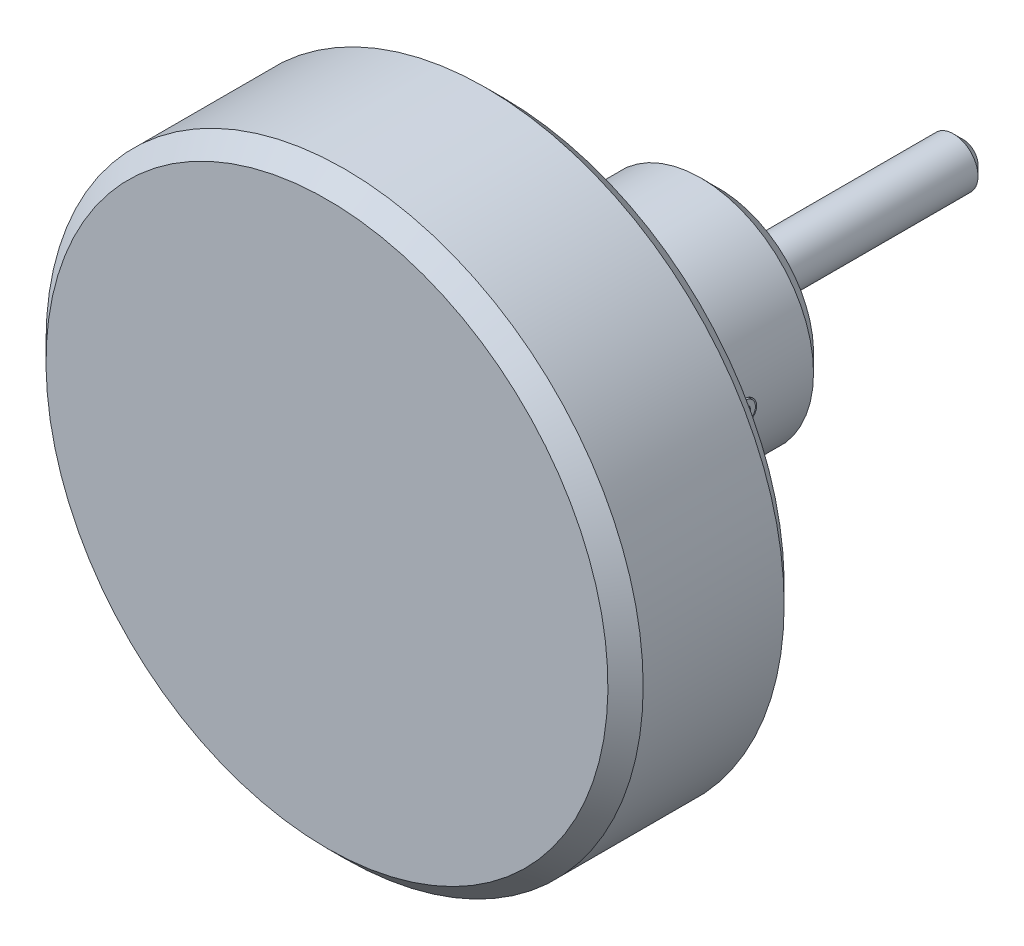
SolidWorks part; units mm, degrees
ref_plane "Front" through (0, 0, 0) normal (0, 0, 1) x (1, 0, 0)
ref_plane "Top" through (0, 0, 0) normal (0, 1, 0) x (1, 0, 0)
ref_plane "Right" through (0, 0, 0) normal (1, 0, 0) x (0, 0, -1)
sketch "Sketch0" plane through (0, 0, 0) normal (1, 0, 0) x (0, 0, -1)
  line L0 (12.5, 0) -> (-12.5, 0) construction
  line L1 (-22.4906, 0) -> (-21.9826, 0) construction
  line L2 (12.4375, 2.6083) -> (12.9375, 1.7422) construction
  line L3 (12.9375, 1.7422) -> (13.4375, 2.6083) construction
  line L4 (-12.5, 2.5) -> (12.5, 2.5) construction
  line L5 (12.5, 2.5) -> (12.5, 0) construction
  line L6 (-12.5, 0) -> (-12.5, 2.5) construction
  line L8 (13.4375, 2.6083) -> (12.4375, 2.6083) construction
  line L9 (12.9375, 1.7422) -> (12.9375, 1.8505) construction
  line L10 (-12.5, -2.5) -> (12.5, -2.5) construction
  line L11 (12.9375, 2.6083) -> (12.9375, 2.5) construction
  line L12 (12.5, 2.5) -> (13.375, 2.5) construction
  line L13 (12.4688, 2.5541) -> (13.4062, 2.5541) construction
  line L14 (12.875, 1.8505) -> (13, 1.8505) construction
  line L15 (-12.5, 0) -> (-52.5, 0) construction
  line L16 (-52.5, -30.5) -> (-52.5, 30.5) construction
  line L17 (-52.5, 30.5) -> (-34.5, 30.5) construction
  line L18 (-34.5, 30.5) -> (-34.5, 11.5) construction
  line L19 (-34.5, 11.5) -> (-12.5, 11.5) construction
  line L20 (-12.5, 11.5) -> (-12.5, 0) construction
  circle A0 centre (-21.3, 0) radius 1.1906
  point P2 (-21.3, 0)
  point P17 (8, -2.5)
  point P18 (12.9375, 2.5)
  point P19 (0, 0)
  point P22 (12.9375, 2.5541)
  point P26 (12.9375, 1.8505)
  point P43 (-52.5, 0)
  dimension "Roll Pin Diameter" = 2.3813
  dimension "Thread Pitch" = 1
  dimension "D1" = 0.125
  dimension "D2" = 4.5
  dimension "Stud Diameter | Thread Size" = 5
  dimension "Head Height" = 18
  dimension "Head Diameter" = 61
  dimension "Hub Diameter" = 23
  dimension "Stud Length" = 25
  dimension "D3" = 8.8
  dimension "Roll Pin Wall Thickness" = 0.508
  dimension "Hub Height" = 22
sketch "Sketch1" plane through (0, 0, 0) normal (1, 0, 0) x (0, 0, -1)
  line L0 (12.5, 0) -> (-12.5, 0)
  line L4 (-12.5, 2.5) -> (12.5, 2.5)
  line L5 (12.5, 2.5) -> (12.5, 0)
  line L6 (-12.5, 0) -> (-12.5, 2.5)
revolve "Revolve1" add sketch "Sketch1" angle 360 about L0
sketch "Sketch5" plane through (0, 0, 0) normal (1, 0, 0) x (0, 0, -1)
  line L2 (-12.5, 11.5) -> (-34.5, 11.5)
  line L3 (-34.5, 11.5) -> (-34.5, 30.5)
  line L7 (-52.5, 0) -> (-12.5, 0) construction
  line L10 (-12.5, 11.5) -> (-12.5, 0)
  line L12 (-52.5, 30.5) -> (-34.5, 30.5)
  line L13 (-52.5, 30.5) -> (-52.5, 0)
  line L18 (-12.5, 0) -> (-52.5, 0)
revolve "Revolve3" add sketch "Sketch5" angle 360 about L18
chamfer "Chamfer1" distance 1 angle 45 1 edges at (-2.5, 0, -12.5)
chamfer "Chamfer2" distance 1.8 angle 45 3 edges at (0, 30.5, 34.5) (0, 30.5, 52.5) (0, 11.5, 12.5)
ref_plane "Plane3" through (0, 0, 21.3) normal (0, 0, 1) x (1, 0, 0)
sketch "Sketch16" plane through (0, 0, 21.3) normal (0, 0, 1) x (1, 0, 0)
  line L0 (11.5, 0) -> (1.975, 0)
  line L1 (11.5, 0) -> (11.5, 1.1906)
  line L2 (11.5, 1.1906) -> (1.975, 1.1906)
  line L3 (1.975, 1.1906) -> (1.975, 0)
  circle A0 centre (0, 0) radius 11.5 construction
  circle A1 centre (0, 0) radius 11.5 construction
  point P9 (0, 1.1906)
  dimension "Roll Pin Length" = 9.525
revolve "Cut-Revolve1" cut sketch "Sketch16" angle 360 about L0
sketch "Sketch17" plane through (0, 0, 21.3) normal (0, 0, 1) x (1, 0, 0)
  line L0 (11.5, 1.0656) -> (10.0712, 1.1906)
  line L1 (11.5, 0) -> (11.5, 1.1906) construction
  line L2 (11.5, 1.1906) -> (1.975, 1.1906) construction
  line L3 (10.0712, 1.1906) -> (3.4037, 1.1906)
  line L4 (3.4037, 1.1906) -> (1.975, 1.0656)
  line L5 (1.975, 1.1906) -> (1.975, 0) construction
  line L6 (1.975, 1.0656) -> (1.975, 0.5576)
  line L7 (1.975, 0.5576) -> (3.4037, 0.6826)
  line L8 (3.4037, 0.6826) -> (10.0713, 0.6826)
  line L9 (10.0713, 0.6826) -> (11.5, 0.5576)
  line L10 (11.5, 0.5576) -> (11.5, 1.0656)
  dimension "D1" = 0.508
  dimension "D2" = 5
  dimension "D3" = 1.4287
  dimension "D4" = 0.508
revolve "Revolve4" add sketch "Sketch17" angle 325 mid plane about L0
split "Split1" [suppressed] bodies to split 158
sketch "Sketch13" [suppressed] plane through (0, 0, -10) normal (0, 0, -1) x (-1, 0, 0)
  circle A0 centre (0, 0) radius 2.5 construction
  circle A1 centre (0, 0) radius 2.5
curve "Helix/Spiral1" [suppressed]
sketch "Sketch14" [suppressed] plane through (0, 0, 0) normal (1, 0, 0) x (0, 0, -1)
  line L0 (9.9688, 2.5541) -> (10.9062, 2.5541)
  line L1 (10.9062, 2.5541) -> (10.5, 1.8505)
  line L2 (10.5, 1.8505) -> (10.375, 1.8505)
  line L3 (10.375, 1.8505) -> (9.9688, 2.5541)
sweep "Cut-Sweep1" [suppressed] cut profiles "Sketch14" path "Helix/Spiral1"
sketch "Sketch15" [suppressed] plane through (0, 0, 10) normal (0, 0, -1) x (-1, 0, 0)
  circle A1 centre (0, 0) radius 2.5
  circle A2 centre (0, 0) radius 2.5
  dimension "D1" = 0
extrude "Boss-Extrude1" [suppressed] add sketch "Sketch15" along normal blind 10 draft 45
sketch "Sketch18" [suppressed] plane through (0, 0, 26) normal (0, 0, 1) x (1, 0, 0)
  line L0 (0, 9.5) -> (0, 9.3) construction
  line L1 (0, 9.3) -> (-0.1658, 9.5)
  line L2 (-0.1658, 9.5) -> (0.1658, 9.5)
  line L3 (0.1658, 9.5) -> (0, 9.3)
  line L4 (-0.1658, 9.5) -> (0, 0) construction
  line L5 (0, 0) -> (0.1658, 9.5) construction
  line L6 (0, 9.1) -> (0, 8.9) construction
  line L7 (0, -9.5) -> (0, 9.5) construction
  line L8 (0, 9.1) -> (0, 9.3) construction
  circle A2 centre (0, 0) radius 8.9 construction
  circle A3 centre (0, 0) radius 9.5 construction
  dimension "D1" = 2
sketch "Sketch19" [suppressed] plane through (0, 0, 26) normal (0, 0, 1) x (1, 0, 0)
  circle A0 centre (0, 0) radius 9.5 construction
  circle A1 centre (0, 0) radius 9.5
curve "Helix/Spiral2" [suppressed] pitch 216 height 18 turns 0.0833
sweep "Cut-Sweep2" [suppressed] cut profiles "Sketch18" path "Helix/Spiral2"
pattern_circular "CirPattern1" [suppressed] count 54 over 360 about axis through (0, 0, 12.5) along (0, 0, 1) reverse direction yes of bodies 160
mirror "Mirror1" [suppressed] about plane through (0, 0, 0) normal (1, 0, 0)
equation "\"D1@Chamfer1\" = \"Thread Pitch@Sketch0\""
equation "\"D4@Helix/Spiral1\" = \"Thread Pitch@Sketch0\""
equation "\"D3@Helix/Spiral1\" = \"Thread Pitch@Sketch0\" + \"Stud Length@Sketch0\""
equation "\"D1@Sketch0\" = \"Thread Pitch@Sketch0\" / 8"
equation "\"D2@Sketch0\" = \"Thread Pitch@Sketch0\" * 4.5"
equation "\"D3@Sketch0\"=\"Hub Height@Sketch0\"*0.4"
equation "\"D1@Chamfer2\"=\"Head Height@Sketch0\"*0.1"
equation "\"D1@Sketch17\"=\"Roll Pin Wall Thickness@Sketch0\""
equation "\"D3@Sketch17\"=\"Roll Pin Length@Sketch16\"*0.15"
equation "\"D4@Sketch17\"=\"D1@Sketch17\""
equation "\"D4@Helix/Spiral2\"=\"Head Height@Sketch0\"*12"
equation "\"D3@Helix/Spiral2\"=\"Head Height@Sketch0\""
equation "\"D1@CirPattern1\"=360/(\"D1@Sketch18\"*2)*0.6"
